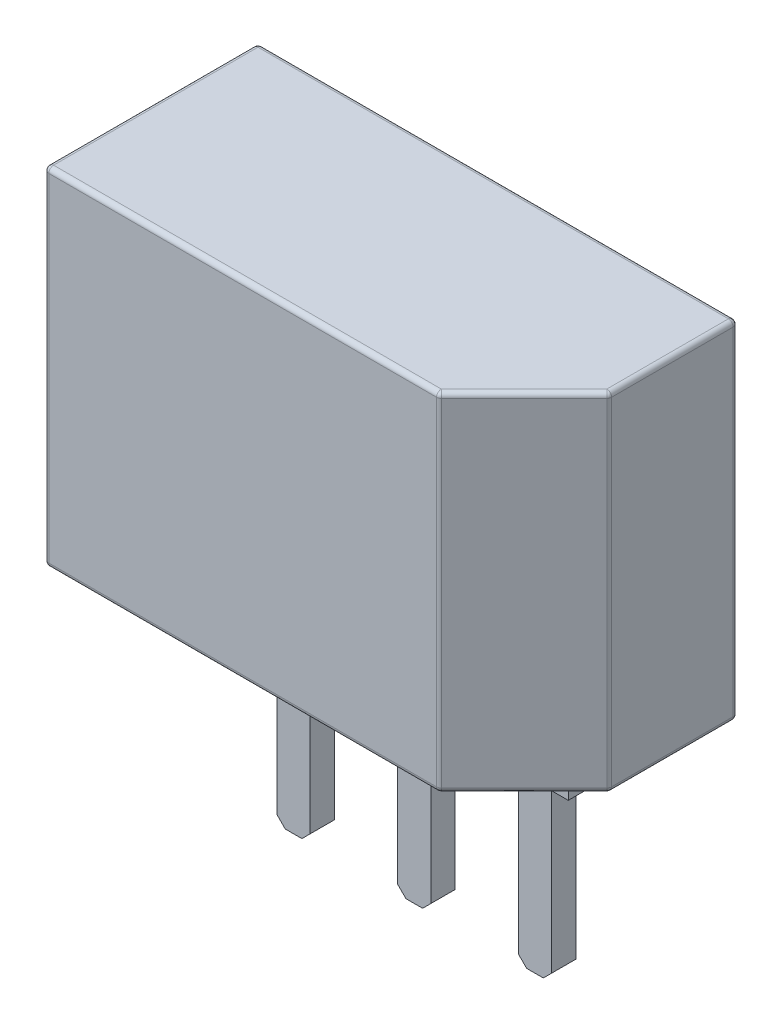
SolidWorks part; units mm, degrees
ref_plane "Ebene vorne" through (0, 0, 0) normal (0, 0, 1) x (1, 0, 0)
ref_plane "Ebene oben" through (0, 0, 0) normal (0, 1, 0) x (1, 0, 0)
ref_plane "Ebene rechts" through (0, 0, 0) normal (1, 0, 0) x (0, 0, -1)
sketch "Skizze1" plane through (0, 0, 0) normal (0, 1, 0) x (1, 0, 0)
  line L1 (-5.05, -2.25) -> (5.05, -2.25)
  line L2 (-5.05, -2.25) -> (-5.05, 2.25)
  line L3 (-5.05, 2.25) -> (5.05, 2.25)
  line L4 (5.05, -2.25) -> (5.05, 2.25)
  line L5 (-5.05, -2.25) -> (5.05, 2.25) construction
  line L6 (-5.05, 2.25) -> (5.05, -2.25) construction
  point P0 (0, 0)
extrude "Aufsatz-Linear austragen1" add sketch "Skizze1" along normal blind 7.3
chamfer "Fase2" distance 1.8 1 edges at (5.05, 3.65, 2.25)
ref_plane "Ebene2" through (0, 0, -0.745) normal (0, 0, 1) x (1, 0, 0)
sketch "Skizze3" plane through (0, 0, -0.745) normal (0, 0, 1) x (1, 0, 0)
  line L0 (-0.7, 0) -> (0.7, 0)
  line L1 (-0.7, 0) -> (-0.7, -1.5)
  line L2 (-0.7, -1.5) -> (-0.35, -1.5)
  line L3 (0.35, -1.5) -> (0.35, -4.825)
  line L4 (0.175, -5) -> (-0.175, -5)
  line L5 (-0.35, -1.5) -> (-0.35, -4.825)
  line L6 (0.35, -1.5) -> (0.7, -1.5)
  line L7 (0.7, -1.5) -> (0.7, 0)
  line L8 (0.35, -4.825) -> (0.175, -5)
  line L9 (-0.35, -4.825) -> (-0.175, -5)
  line L10 (0, -5) -> (0, 0) construction
  point P0 (0, 0)
  dimension "D1" = 1.4
  dimension "D2" = 1.5
  dimension "D3" = 3.5
  dimension "D4" = 0.7
  dimension "D5" = 45
  dimension "D6" = 0.35
extrude "Aufsatz-Linear austragen2" add sketch "Skizze3" along normal blind 0.255 and the other way blind 0.255
pattern_linear "Lineares Muster1" count 2 spacing 2.54 along (1, 0, 0) count 2 spacing 2.54 along (-1, 0, 0) of "Aufsatz-Linear austragen2"
fillet "Verrundung1" radius 0.1 27 edges at (5.05, 3.65, -2.25) (-5.05, 3.65, -2.25) (-5.05, 3.65, 2.25) (-5.05, 7.3, 0) (0, 7.3, -2.25) (5.05, 7.3, -0.9) (-0.9, 7.3, 2.25) (2.54, 0, -0.49) (1.84, 0, -0.745) (2.54, 0, -1) (3.24, 0, -0.745) (0, 0, -0.49) (-0.7, 0, -0.745) (0, 0, -1) (0.7, 0, -0.745) (0, 0, -2.25) (-5.05, 0, 0) (-0.9, 0, 2.25) (5.05, 0, -0.9) (-2.54, 0, -0.49) (-3.24, 0, -0.745) (-2.54, 0, -1) (-1.84, 0, -0.745) (5.05, 3.65, 0.45) (4.15, 0, 1.35) (3.25, 3.65, 2.25) (4.15, 7.3, 1.35)
